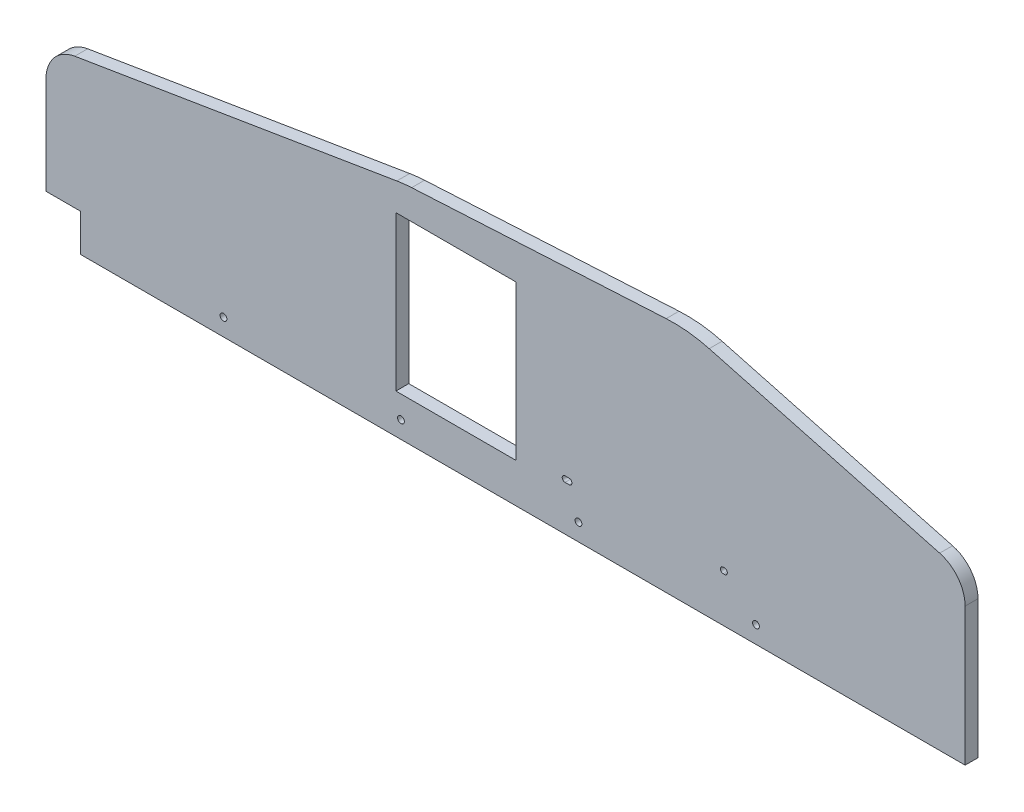
SolidWorks part; units mm, degrees
material "PC High Viscosity"
ref_plane "Front Plane" through (0, 0, 0) normal (0, 0, 1) x (1, 0, 0)
ref_plane "Top Plane" through (0, 0, 0) normal (0, 1, 0) x (1, 0, 0)
ref_plane "Right Plane" through (0, 0, 0) normal (1, 0, 0) x (0, 0, -1)
sketch "Sketch2" plane through (0, 0, 0) normal (0, 0, 1) x (1, 0, 0)
  line L0 (-340, 26.4) -> (-340, 121.4)
  line L1 (135, 176.4) -> (-75, 165)
  line L2 (135, 176.4) -> (340, 121.4)
  line L3 (340, 121.4) -> (340, 26.4)
  line L4 (340, 26.4) -> (340, 0)
  line L5 (-75, 165) -> (-340, 121.4)
  line L6 (340, 0) -> (-340, 0)
  line L7 (-340, 0) -> (-340, 26.4)
  dimension "D1" = 165
  dimension "D2" = 680
  dimension "D3" = 95
  dimension "D4" = 475
  dimension "D5" = 150
  dimension "D6" = 210
  dimension "D8" = 95
  dimension "D9" = 26.4
extrude "Boss-Extrude1" add sketch "Sketch2" along normal mid plane 9.525
fillet "Fillet1" radius 25.4 2 edges at (340, 121.4, 0) (-340, 121.4, 0)
fillet "Fillet2" radius 101.6 2 edges at (-75, 165, 0) (135, 176.4, 0)
sketch "Sketch3" plane through (0, 0, 4.7625) normal (0, 0, 1) x (1, 0, 0)
  line L0 (0, 0) -> (0, 192.0016) construction
  line L1 (-340, 0) -> (-314.6, 0)
  line L2 (-340, 0) -> (-340, 27.686)
  line L3 (-340, 27.686) -> (-314.6, 27.686)
  line L4 (-314.6, 0) -> (-314.6, 27.686)
  line L5 (0, 192.0016) -> (0, -60.0751) construction
  dimension "D1" = 25.4
  dimension "D2" = 27.686
extrude "Cut-Extrude1" cut sketch "Sketch3" against normal through all
sketch "Sketch5" plane through (0, 0, 4.7625) normal (0, 0, 1) x (1, 0, 0)
  line L1 (-314.6, 0) -> (340, 0) construction
  line L3 (-81.1185, 29.1465) -> (7.7815, 29.1465)
  line L5 (7.7815, 29.1465) -> (7.7815, 143.4465)
  line L6 (7.7815, 143.4465) -> (-81.1185, 143.4465)
  line L7 (340, 0) -> (340, 101.9164) construction
  line L8 (-81.1185, 29.1465) -> (-81.1185, 143.4465)
  dimension "D2" = 29.1465
  dimension "D1" = 332.2185
  dimension "D3" = 114.3
  dimension "D4" = 88.9
extrude "Cut-Extrude2" cut sketch "Sketch5" against normal through all
hole_wizard "Tap Drill for M6x1.0 Tap1" positions "Sketch7" profile "Sketch6" hole size "M6x1.0" standard "ANSI Metric" end condition through all
sketch "Sketch7" plane through (0, 0, 4.7625) normal (0, 0, 1) x (1, 0, 0)
  line L0 (-314.6, 0) -> (340, 0) construction
  line L1 (-340, 99.8375) -> (-340, 27.686) construction
  point P0 (-208.682, 12.7)
  point P2 (-77.364, 12.7)
  point P4 (53.954, 12.7)
  point P6 (185.272, 12.7)
  dimension "D1" = 12.7
  dimension "D2" = 131.318
  dimension "D3" = 131.318
  dimension "D4" = 131.318
  dimension "D5" = 131.318
sketch "Sketch6" plane through (-208.682, 12.7, 4.7625) normal (1, 0, 0) x (0, -1, 0)
  line L0 (0, 0) -> (0, 9.525)
  line L1 (0, 9.525) -> (2.5, 9.525)
  line L2 (2.5, 9.525) -> (2.5, 0)
  line L5 (2.5, 0) -> (0, 0)
  line L11 (0, -6.35) -> (0, 107.95) construction
  dimension "Thru Hole Dia." = 5
  dimension "Thru Hole Depth" = 9.525
sketch "Sketch8" plane through (0, 0, 4.7625) normal (0, 0, 1) x (1, 0, 0)
  line L0 (161, 35.3) -> (162, 35.3) construction
  line L1 (161, 37.4) -> (162, 37.4)
  line L2 (161, 33.2) -> (162, 33.2)
  line L3 (47, 35.3) -> (44, 35.3) construction
  line L4 (47, 33.2) -> (44, 33.2)
  line L5 (47, 37.4) -> (44, 37.4)
  line L6 (-314.6, 0) -> (340, 0) construction
  line L10 (-340, 99.8375) -> (-340, 27.686) construction
  arc A0 (161, 37.4) -> (161, 33.2) centre (161, 35.3) ccw
  arc A1 (162, 33.2) -> (162, 37.4) centre (162, 35.3) ccw
  arc A2 (47, 33.2) -> (47, 37.4) centre (47, 35.3) ccw
  arc A3 (44, 37.4) -> (44, 33.2) centre (44, 35.3) ccw
  point P2 (161.5, 35.3)
  point P9 (45.5, 35.3)
  dimension "D2" = 1
  dimension "D1" = 2.1
  dimension "D3" = 35.3
  dimension "D4" = 384
  dimension "D5" = 115.5
  dimension "D6" = 3
extrude "Cut-Extrude3" cut sketch "Sketch8" against normal through all
